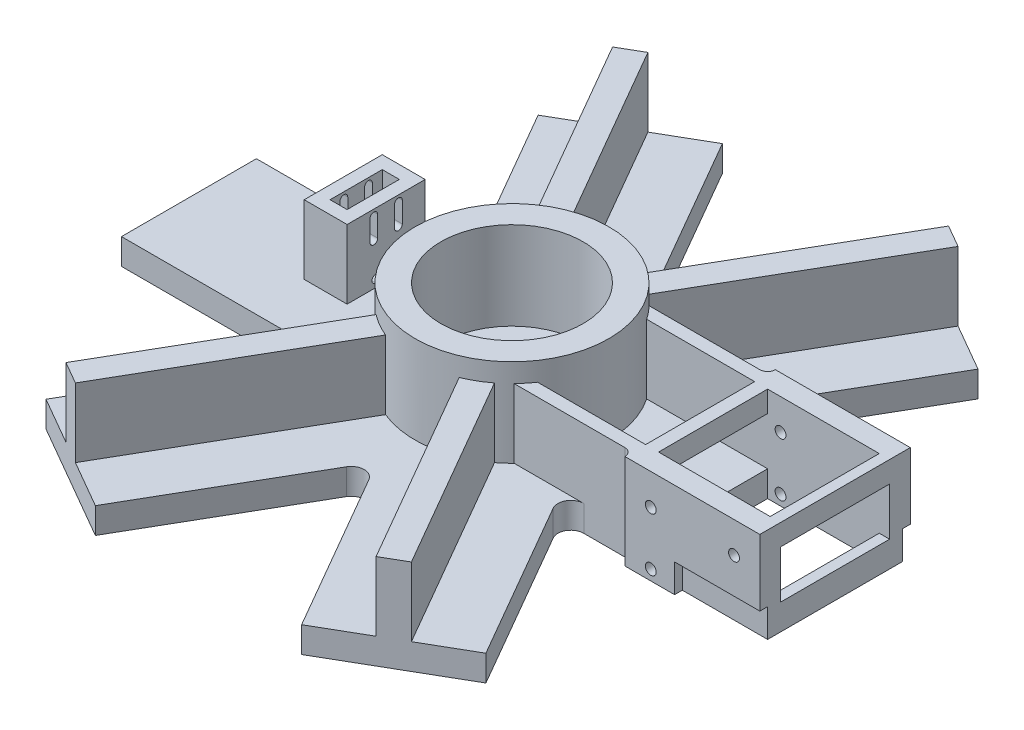
SolidWorks part; units mm, degrees
ref_plane "Ebene vorne" through (0, 0, 0) normal (0, 0, 1) x (1, 0, 0)
ref_plane "Ebene oben" through (0, 0, 0) normal (0, 1, 0) x (1, 0, 0)
ref_plane "Ebene rechts" through (0, 0, 0) normal (1, 0, 0) x (0, 0, -1)
sketch "Skizze1" plane through (0, 0, 0) normal (0, 1, 0) x (1, 0, 0)
  line L5 (-125, 26.1) -> (-125, -26.1)
  line L6 (-125, -26.1) -> (-53.8668, -26.1)
  line L14 (-125, 26.1) -> (-53.8668, 26.1)
  line L15 (53.8668, 26.1) -> (125, 26.1)
  line L16 (125, 26.1) -> (125, -26.1)
  line L17 (125, -26.1) -> (53.8668, -26.1)
  line L18 (125, 0) -> (-125, 0) construction
  line L19 (62.5, -108.2532) -> (-62.5, 108.2532) construction
  line L20 (-62.5, -108.2532) -> (62.5, 108.2532) construction
  line L21 (-85.1033, 95.2032) -> (-39.8967, 121.3032)
  line L22 (-39.8967, 121.3032) -> (-4.3301, 59.7)
  line L23 (-85.1033, 95.2032) -> (-49.5367, 33.6)
  line L24 (4.3301, 59.7) -> (39.8967, 121.3032)
  line L25 (39.8967, 121.3032) -> (85.1033, 95.2032)
  line L26 (85.1033, 95.2032) -> (49.5367, 33.6)
  line L27 (-49.5367, -33.6) -> (-85.1033, -95.2032)
  line L28 (-85.1033, -95.2032) -> (-39.8967, -121.3032)
  line L29 (-39.8967, -121.3032) -> (-4.3301, -59.7)
  line L30 (4.3301, -59.7) -> (39.8967, -121.3032)
  line L31 (39.8967, -121.3032) -> (85.1033, -95.2032)
  line L32 (85.1033, -95.2032) -> (49.5367, -33.6)
  circle A0 centre (0, 0) radius 37.5 construction
  circle A1 centre (0, 0) radius 125 construction
  arc A3 (-4.3301, -59.7) -> (4.3301, -59.7) centre (0, -62.2) cw
  arc A4 (49.5367, -33.6) -> (53.8668, -26.1) centre (53.8668, -31.1) cw
  arc A5 (53.8668, 26.1) -> (49.5367, 33.6) centre (53.8668, 31.1) cw
  arc A6 (4.3301, 59.7) -> (-4.3301, 59.7) centre (0, 62.2) cw
  arc A7 (-49.5367, 33.6) -> (-53.8668, 26.1) centre (-53.8668, 31.1) cw
  arc A8 (-49.5367, -33.6) -> (-53.8668, -26.1) centre (-53.8668, -31.1) ccw
  point P18 (-125, 0)
  point P19 (-62.5, 108.2532)
  point P35 (62.5, 108.2532)
  point P38 (62.5, -108.2532)
  point P39 (-62.5, -108.2532)
  dimension "D2" = 75
  dimension "D1" = 250
  dimension "D3" = 60
  dimension "D6" = 5
  dimension "D4" = 60
  dimension "D5" = 52.2
extrude "Aufsatz-Linear austragen1" add sketch "Skizze1" along normal blind 10
sketch "Skizze2" plane through (0, 10, 0) normal (0, 1, 0) x (1, 0, 0)
  circle A0 centre (0, 0) radius 27.5
  circle A1 centre (0, 0) radius 37.5
  dimension "D1" = 75
  dimension "D2" = 55
extrude "Aufsatz-Linear austragen2" add sketch "Skizze2" along normal blind 34
sketch "Skizze3" plane through (0, 10, 0) normal (0, 1, 0) x (1, 0, 0)
  line L0 (125, 26.1) -> (72.8, 26.1)
  line L1 (125, 26.1) -> (53.8668, 26.1) construction
  line L2 (72.8, 26.1) -> (72.8, -26.1)
  line L3 (53.8668, -26.1) -> (125, -26.1) construction
  line L4 (72.8, -26.1) -> (125, -26.1)
  line L5 (125, -26.1) -> (125, -21.1)
  line L6 (125, -26.1) -> (125, 26.1) construction
  line L7 (125, -21.1) -> (77.8, -21.1)
  line L8 (77.8, -21.1) -> (77.8, 21.1)
  line L9 (77.8, 21.1) -> (125, 21.1)
  line L10 (125, 21.1) -> (125, 26.1)
  dimension "D1" = 5
  dimension "D2" = 47.2
  dimension "D3" = 5
extrude "Aufsatz-Linear austragen3" add sketch "Skizze3" along normal blind 35.4
sketch "Skizze4" plane through (0, 10, 0) normal (0, 1, 0) x (1, 0, 0)
  line L1 (77.8, 21.1) -> (125, 21.1)
  line L2 (77.8, 21.1) -> (77.8, -21.1)
  line L3 (77.8, -21.1) -> (125, -21.1)
  line L4 (125, 21.1) -> (125, -21.1)
  line L5 (77.8, 21.1) -> (125, -21.1) construction
  line L6 (77.8, -21.1) -> (125, 21.1) construction
  point P4 (101.4, 0)
extrude "Schnitt-Linear austragen1" cut sketch "Skizze4" against normal through all
sketch "Skizze8" plane through (0, 10, 0) normal (0, 1, 0) x (1, 0, 0)
  line L1 (-75.3, 25.1) -> (-58.7, 25.1)
  line L2 (-75.3, 25.1) -> (-75.3, -5.1)
  line L3 (-75.3, -5.1) -> (-58.7, -5.1)
  line L4 (-58.7, 25.1) -> (-58.7, -5.1)
  line L5 (-75.3, 25.1) -> (-58.7, -5.1) construction
  line L6 (-75.3, -5.1) -> (-58.7, 25.1) construction
  line L10 (-70.3, 20.1) -> (-70.3, -0.1)
  line L11 (-70.3, -0.1) -> (-63.7, -0.1)
  line L12 (-63.7, 20.1) -> (-63.7, -0.1)
  line L13 (-70.3, 20.1) -> (-63.7, 20.1)
  line L14 (65, 0) -> (-69, 0) construction
  line L15 (-67, -0.1) -> (-65, 0) construction
  line L16 (-67, -0.1) -> (-69, 0) construction
  circle A0 centre (0, 0) radius 69 construction
  circle A1 centre (0, 0) radius 65 construction
  point P4 (-67, 10)
  dimension "D4" = 130
  dimension "D5" = 138
  dimension "D1" = 30.2
  dimension "D2" = 16.6
  dimension "D6" = 0.1
  dimension "D3" = 5
extrude "Aufsatz-Linear austragen4" add sketch "Skizze8" along normal blind 26.7
sketch "Skizze10" plane through (-75.3, 0, 0) normal (-1, 0, 0) x (0, 0, 1)
  line L0 (-14.75, 34.2) -> (-14.75, 26.2) construction
  line L1 (-13.25, 34.2) -> (-13.25, 26.2)
  line L2 (-16.25, 34.2) -> (-16.25, 26.2)
  line L3 (-5.25, 34.2) -> (-5.25, 26.2) construction
  line L4 (-3.75, 34.2) -> (-3.75, 26.2)
  line L5 (-6.75, 34.2) -> (-6.75, 26.2)
  line L6 (-14, 13) -> (-6, 13) construction
  line L7 (-14, 14.5) -> (-6, 14.5)
  line L8 (-14, 11.5) -> (-6, 11.5)
  line L9 (-10, 36.7) -> (-10, 10) construction
  line L10 (-25.1, 36.7) -> (5.1, 36.7) construction
  line L11 (-25.1, 10) -> (5.1, 10) construction
  arc A0 (-13.25, 34.2) -> (-16.25, 34.2) centre (-14.75, 34.2) ccw
  arc A1 (-16.25, 26.2) -> (-13.25, 26.2) centre (-14.75, 26.2) ccw
  arc A2 (-3.75, 34.2) -> (-6.75, 34.2) centre (-5.25, 34.2) ccw
  arc A3 (-6.75, 26.2) -> (-3.75, 26.2) centre (-5.25, 26.2) ccw
  arc A4 (-14, 14.5) -> (-14, 11.5) centre (-14, 13) ccw
  arc A5 (-6, 11.5) -> (-6, 14.5) centre (-6, 13) ccw
  point P2 (-14.75, 30.2)
  point P7 (-5.25, 30.2)
  point P14 (-10, 13)
  point P21 (-10, 11.5)
  dimension "D1" = 3
  dimension "D2" = 3
  dimension "D3" = 8
  dimension "D4" = 8
  dimension "D5" = 3
  dimension "D6" = 8
  dimension "D7" = 4.75
  dimension "D8" = 4.75
  dimension "D9" = 2.5
  dimension "D10" = 2.5
  dimension "D11" = 3
extrude "Schnitt-Linear austragen6" cut sketch "Skizze10" against normal up to surface (16.6 mm away) up to face at (-58.7, 23.35, -10)
sketch "Skizze11" plane through (0, 10, 0) normal (0, 1, 0) x (1, 0, 0)
  line L0 (-66.8301, 105.7532) -> (-58.1699, 110.7532)
  line L1 (-39.8967, 121.3032) -> (-85.1033, 95.2032) construction
  line L2 (-58.1699, 110.7532) -> (-14.2525, 34.686)
  line L3 (-66.8301, 105.7532) -> (-22.9127, 29.686)
  line L4 (-4.3301, 59.7) -> (-39.8967, 121.3032) construction
  line L5 (-85.1033, 95.2032) -> (-39.8967, 121.3032) construction
  line L6 (58.1699, 110.7532) -> (14.2525, 34.686)
  line L7 (85.1033, 95.2032) -> (39.8967, 121.3032) construction
  line L8 (58.1699, 110.7532) -> (66.8301, 105.7532)
  line L9 (66.8301, 105.7532) -> (22.9127, 29.686)
  line L10 (-58.1699, -110.7532) -> (-14.2525, -34.686)
  line L11 (-85.1033, -95.2032) -> (-39.8967, -121.3032) construction
  line L12 (-58.1699, -110.7532) -> (-66.8301, -105.7532)
  line L13 (-66.8301, -105.7532) -> (-22.9127, -29.686)
  line L14 (66.8301, -105.7532) -> (58.1699, -110.7532)
  line L15 (39.8967, -121.3032) -> (85.1033, -95.2032) construction
  line L16 (58.1699, -110.7532) -> (14.2525, -34.686)
  line L17 (66.8301, -105.7532) -> (22.9127, -29.686)
  line L18 (-85.1033, -95.2032) -> (-39.8967, -121.3032) construction
  line L19 (39.8967, -121.3032) -> (85.1033, -95.2032) construction
  line L21 (39.8967, 121.3032) -> (85.1033, 95.2032) construction
  line L23 (77.8, 21.1) -> (125, 21.1) construction
  line L24 (72.8, 26.1) -> (26.9266, 26.1)
  line L25 (72.8, 26.1) -> (72.8, 21.1)
  line L26 (72.8, 21.1) -> (26.9266, 21.1)
  line L27 (26.9266, 26.1) -> (26.9266, 21.1)
  line L28 (72.8, 26.1) -> (26.9266, 21.1) construction
  line L29 (72.8, 21.1) -> (26.9266, 26.1) construction
  line L30 (72.8, -26.1) -> (26.9266, -26.1)
  line L31 (72.8, -26.1) -> (72.8, -21.1)
  line L32 (72.8, -21.1) -> (26.9266, -21.1)
  line L33 (26.9266, -26.1) -> (26.9266, -21.1)
  line L34 (72.8, -26.1) -> (26.9266, -21.1) construction
  line L35 (72.8, -21.1) -> (26.9266, -26.1) construction
  line L36 (125, -21.1) -> (77.8, -21.1) construction
  circle A0 centre (0, 0) radius 37.5 construction
  circle A1 centre (0, 0) radius 37.5 construction
  arc A3 (-22.9127, 29.686) -> (-14.2525, 34.686) centre (0, 0) cw
  arc A4 (-22.9127, -29.686) -> (-14.2525, -34.686) centre (0, 0) ccw
  arc A5 (22.9127, -29.686) -> (14.2525, -34.686) centre (0, 0) cw
  arc A6 (22.9127, 29.686) -> (14.2525, 34.686) centre (0, 0) ccw
  point P16 (-62.5, 108.2532)
  point P17 (-62.5, 108.2532)
  point P20 (62.5, -108.2532)
  point P45 (62.5, -108.2532)
  point P46 (62.5, 108.2532)
  point P49 (62.5, 108.2532)
  point P51 (-62.5, -108.2532)
  point P52 (-62.5, -108.2532)
  point P61 (49.8633, 23.6)
  point P67 (49.8633, -23.6)
  dimension "D1" = 10
extrude "Aufsatz-Linear austragen5" add sketch "Skizze11" along normal up to surface (26.7 mm away) up to face at (-67, 36.7, -10)
sketch "Skizze12" plane through (0, 45.4, 0) normal (0, 1, 0) x (1, 0, 0)
  line L0 (72.8, 26.1) -> (72.8, -26.1) construction
  line L1 (125, -26.1) -> (72.8, -26.1)
  line L2 (125, -26.1) -> (125, 26.1)
  line L3 (125, 26.1) -> (72.8, 26.1)
  line L4 (72.8, -26.1) -> (72.8, 26.1)
  line L5 (125, -26.1) -> (72.8, 26.1) construction
  line L6 (125, 26.1) -> (72.8, -26.1) construction
  point P4 (98.9, 0)
extrude "Schnitt-Linear austragen7" cut sketch "Skizze12" against normal up to surface (8.7 mm away) up to face at (50.9087, 36.7, 23.6219)
sketch "Skizze13" plane through (0, 36.7, 0) normal (0, 1, 0) x (1, 0, 0)
  line L0 (125, 26.1) -> (26.9266, 26.1) construction
  line L1 (125, -26.1) -> (121, -26.1)
  line L2 (125, -26.1) -> (125, 26.1)
  line L3 (125, 26.1) -> (121, 26.1)
  line L4 (121, -26.1) -> (121, 26.1)
  line L5 (125, -26.1) -> (121, 26.1) construction
  line L6 (125, 26.1) -> (121, -26.1) construction
  point P4 (123, 0)
  dimension "D1" = 4
extrude "Aufsatz-Linear austragen6" add sketch "Skizze13" against normal up to surface (36.7 mm away) up to face at (14.4857, 0, 0)
sketch "Skizze14" plane through (125, 0, 0) normal (1, 0, 0) x (0, 0, -1)
  line L0 (-26.1, 36.7) -> (-26.1, 0) construction
  line L1 (-21.1, 28.5) -> (21.1, 28.5)
  line L2 (-21.1, 28.5) -> (-21.1, 10)
  line L3 (-21.1, 10) -> (21.1, 10)
  line L4 (21.1, 28.5) -> (21.1, 10)
  line L5 (-21.1, 28.5) -> (21.1, 10) construction
  line L6 (-21.1, 10) -> (21.1, 28.5) construction
  line L7 (26.1, 36.7) -> (-26.1, 36.7) construction
  line L8 (-26.1, 0) -> (26.1, 0) construction
  line L9 (26.1, 36.7) -> (26.1, 10) construction
  point P4 (0, 19.25)
  dimension "D1" = 5
  dimension "D2" = 8.2
  dimension "D3" = 10
  dimension "D4" = 5
extrude "Schnitt-Linear austragen8" cut sketch "Skizze14" against normal up to surface (52.2 mm away) up to face at (72.8, 23.35, 0)
sketch "Skizze15" plane through (0, 36.7, 0) normal (0, 1, 0) x (1, 0, 0)
  line L1 (125, 26.1) -> (72.8, 26.1)
  line L2 (125, 26.1) -> (125, 29.1)
  line L3 (125, 29.1) -> (72.8, 29.1)
  line L4 (72.8, 26.1) -> (72.8, 29.1)
  line L5 (125, 26.1) -> (72.8, 29.1) construction
  line L6 (125, 29.1) -> (72.8, 26.1) construction
  line L7 (125, -26.1) -> (72.8, -26.1)
  line L8 (125, -26.1) -> (125, -29.1)
  line L9 (125, -29.1) -> (72.8, -29.1)
  line L10 (72.8, -26.1) -> (72.8, -29.1)
  line L11 (125, -26.1) -> (72.8, -29.1) construction
  line L12 (125, -29.1) -> (72.8, -26.1) construction
  line L13 (72.8, -21.1) -> (72.8, 21.1) construction
  point P4 (98.9, 27.6)
  point P10 (98.9, -27.6)
  dimension "D1" = 3
  dimension "D2" = 3
extrude "Aufsatz-Linear austragen7" add sketch "Skizze15" against normal up to surface (36.7 mm away) up to face at (0, 0, 0)
fillet "Verrundung1" radius 3 2 edges at (72.8, 18.35, -26.1) (72.8, 18.35, 26.1)
sketch "Skizze16" plane through (0, 0, 29.1) normal (0, 0, 1) x (1, 0, 0)
  line L0 (72.8, 0) -> (125, 0) construction
  line L1 (72.8, 36.7) -> (125, 36.7) construction
  line L2 (125, 0) -> (125, 36.7) construction
  line L3 (72.8, 0) -> (72.8, 36.7) construction
  circle A0 centre (82.8, 24.7) radius 2.1
  circle A1 centre (115, 24.7) radius 2.1
  circle A3 centre (82.8, 4) radius 2.1
  point P8 (0, 0)
  point P19 (91.9983, -13.2367)
  dimension "D1" = 4.2
  dimension "D3" = 12
  dimension "D4" = 10
  dimension "D5" = 10
  dimension "D6" = 12
  dimension "D8" = 10
  dimension "D9" = 4
extrude "Schnitt-Linear austragen9" cut sketch "Skizze16" against normal up to surface (58.2 mm away) up to face at (98.9, 18.35, -29.1)
sketch "Skizze17" plane through (0, 0, 0) normal (0, -1, 0) x (1, 0, 0)
  line L2 (125, 29.1) -> (92, 29.1)
  line L3 (125, 29.1) -> (125, 26.1)
  line L4 (125, 26.1) -> (92, 26.1)
  line L5 (92, 29.1) -> (92, 26.1)
  line L6 (125, 29.1) -> (92, 26.1) construction
  line L7 (125, 26.1) -> (92, 29.1) construction
  line L8 (125, -29.1) -> (92, -29.1)
  line L9 (125, -29.1) -> (125, -26.1)
  line L10 (125, -26.1) -> (92, -26.1)
  line L11 (92, -29.1) -> (92, -26.1)
  line L12 (125, -29.1) -> (92, -26.1) construction
  line L13 (125, -26.1) -> (92, -29.1) construction
  point P6 (108.5, 27.6)
  point P10 (108.5, -27.6)
  dimension "D1" = 3
  dimension "D2" = 3
  dimension "D3" = 33
  dimension "D4" = 33
extrude "Schnitt-Linear austragen10" cut sketch "Skizze17" against normal blind 11
equation "\"D3@Skizze3\"=\"D1@Skizze3\""
equation "\"D2@Skizze10\"=\"D1@Skizze10\""
equation "\"D4@Skizze10\"=\"D3@Skizze10\""
equation "\"D5@Skizze10\"= \"D2@Skizze10\""
equation "\"D6@Skizze10\"=\"D3@Skizze10\""
equation "\"D8@Skizze10\"=\"D7@Skizze10\""
equation "\"D10@Skizze10\"=\"D9@Skizze10\""
